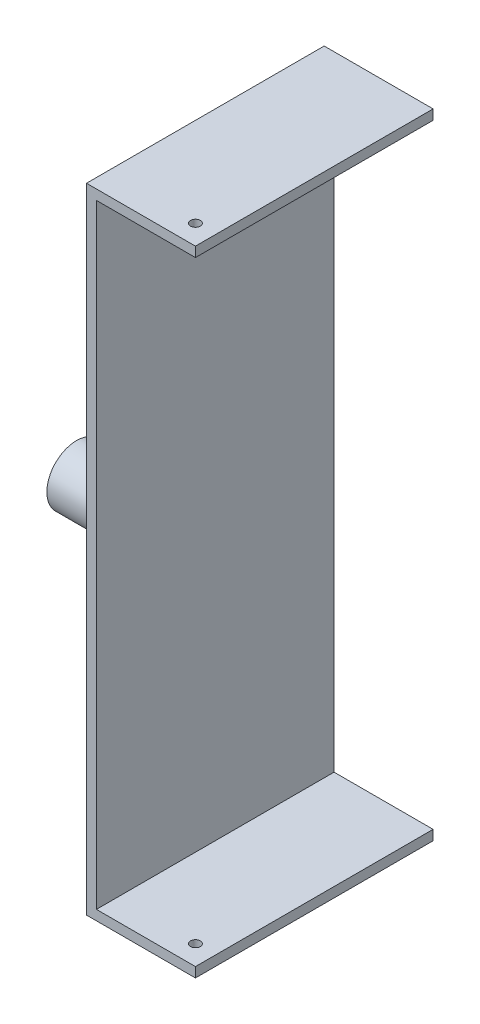
SolidWorks part; units mm, degrees
ref_plane "Front Plane" through (0, 0, 0) normal (0, 0, 1) x (1, 0, 0)
ref_plane "Top Plane" through (0, 0, 0) normal (0, 1, 0) x (1, 0, 0)
ref_plane "Right Plane" through (0, 0, 0) normal (1, 0, 0) x (0, 0, -1)
sketch "Sketch1" plane through (0, 0, 0) normal (0, 0, 1) x (1, 0, 0)
  line L0 (-5, 5) -> (50, 5)
  line L1 (0, 0) -> (50, 0)
  line L2 (0, 0) -> (0, -310)
  line L3 (0, -310) -> (50, -310)
  line L5 (-5, 5) -> (-5, -315)
  line L6 (-5, -315) -> (50, -315)
  line L7 (50, 5) -> (50, 0)
  line L8 (50, -310) -> (50, -315)
  dimension "D1" = 310
  dimension "D3" = 55
  dimension "D2" = 5
extrude "Boss-Extrude1" add sketch "Sketch1" along normal blind 120
sketch "Sketch2" plane through (-5, 0, 0) normal (-1, 0, 0) x (0, 0, 1)
  line L4 (120, 5) -> (120, -315) construction
  circle A0 centre (90, -155) radius 15
  point P12 (120, -155)
  dimension "D1" = 30
  dimension "D2" = 30
extrude "Boss-Extrude2" add sketch "Sketch2" along normal blind 35
sketch "Sketch3" plane through (0, -315, 0) normal (0, -1, 0) x (1, 0, 0)
  line L0 (50, 120) -> (50, 0) construction
  line L1 (-5, 120) -> (50, 120) construction
  circle A0 centre (40, 110) radius 2.5
  dimension "D1" = 5
  dimension "D2" = 10
  dimension "D3" = 10
extrude "Cut-Extrude1" cut sketch "Sketch3" against normal blind 320
